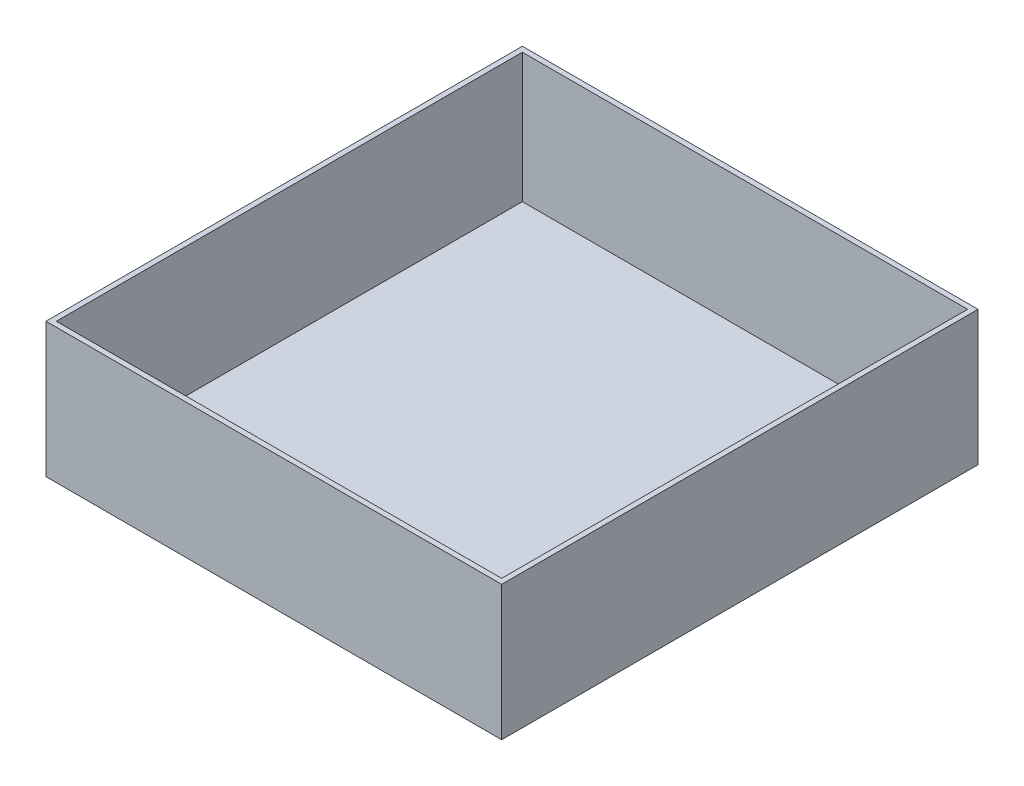
SolidWorks part; units mm, degrees
ref_plane "Front Plane" through (0, 0, 0) normal (0, 0, 1) x (1, 0, 0)
ref_plane "Top Plane" through (0, 0, 0) normal (0, 1, 0) x (1, 0, 0)
ref_plane "Right Plane" through (0, 0, 0) normal (1, 0, 0) x (0, 0, -1)
sketch "Sketch1" plane through (0, 0, 0) normal (0, 1, 0) x (1, 0, 0)
  line L1 (0, 0) -> (279.4, 0)
  line L2 (0, 0) -> (0, 292.1)
  line L3 (0, 292.1) -> (279.4, 292.1)
  line L4 (279.4, 0) -> (279.4, 292.1)
  dimension "D1" = 279.4
  dimension "D2" = 292.1
extrude "Boss-Extrude1" add sketch "Sketch1" along normal blind 82.55
sketch "Sketch3" plane through (0, 82.55, 0) normal (0, 1, 0) x (1, 0, 0)
  line L14 (3.175, 3.175) -> (276.225, 3.175)
  line L15 (276.225, 3.175) -> (276.225, 288.925)
  line L16 (3.175, 288.925) -> (3.175, 3.175)
  line L17 (276.225, 288.925) -> (3.175, 288.925)
  line L18 (3.175, 3.175) -> (276.225, 3.175)
  line L19 (276.225, 3.175) -> (276.225, 288.925)
  line L20 (3.175, 288.925) -> (3.175, 3.175)
  line L21 (276.225, 288.925) -> (3.175, 288.925)
  dimension "D1" = 3.175
extrude "Cut-Extrude1" cut sketch "Sketch3" against normal blind 79.375
